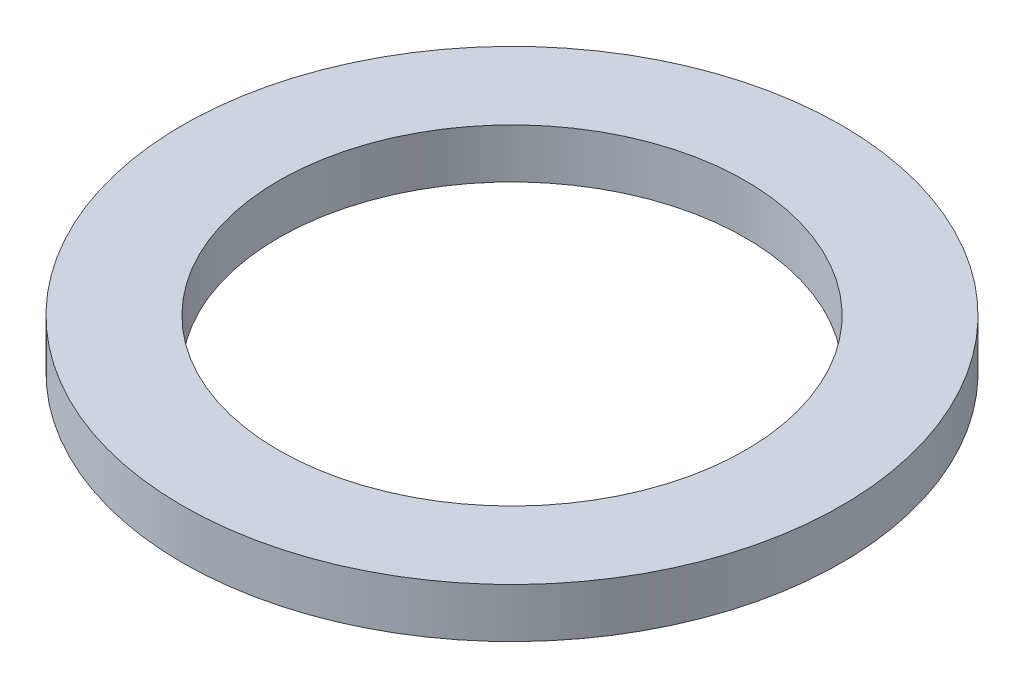
SolidWorks part; units mm, degrees
ref_plane "Front Plane" through (0, 0, 0) normal (0, 0, 1) x (1, 0, 0)
ref_plane "Top Plane" through (0, 0, 0) normal (0, 1, 0) x (1, 0, 0)
ref_plane "Right Plane" through (0, 0, 0) normal (1, 0, 0) x (0, 0, -1)
sketch "Sketch1" plane through (0, 0, 0) normal (0, 1, 0) x (1, 0, 0)
  circle A0 centre (0, 0) radius 60
  dimension "FLANGE_OD" = 120
extrude "Boss-Extrude1" add sketch "Sketch1" along normal blind 9
sketch "Sketch2" plane through (0, 0, 0) normal (0, 1, 0) x (1, 0, 0)
  circle A0 centre (0, 0) radius 42.5
  dimension "BORE_D" = 85
extrude "Cut-Extrude1" cut sketch "Sketch2" along normal through all
sketch "Sketch3" plane through (0, 9, 0) normal (0, 1, 0) x (1, 0, 0)
  circle A0 centre (0, 0) radius 25.3591 construction
  circle A1 centre (-25.3591, 0) radius 3.0553
  dimension "BOLT_D" = 6.1105
  dimension "BOLT_PCD" = 50.7182
extrude "Cut-Extrude2" cut sketch "Sketch3" against normal blind 7.2017 rebuild error yes
pattern_circular "CirPattern1" count 5 over 360 rebuild error yes
